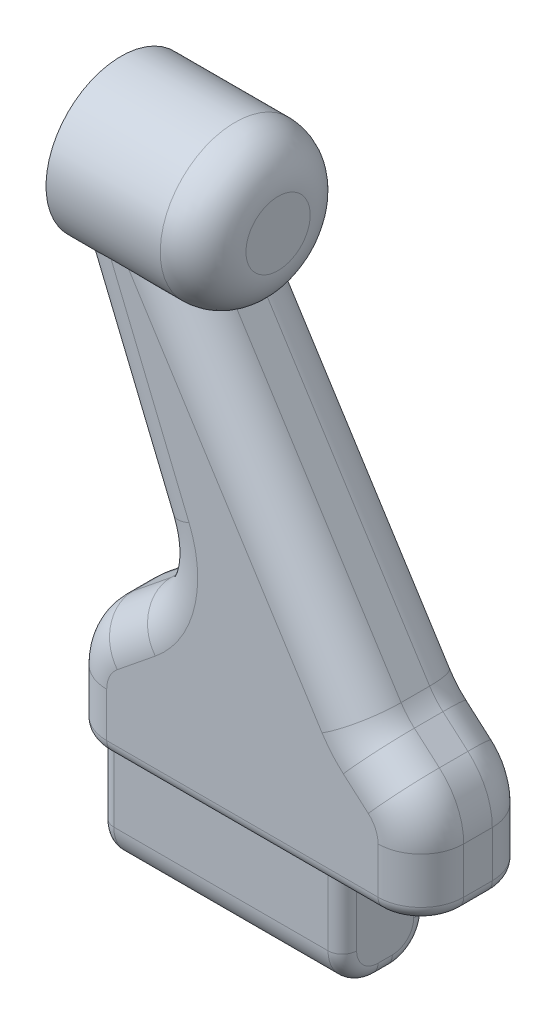
SolidWorks part; units mm, degrees
ref_plane "Front Plane" through (0, 0, 0) normal (0, 0, 1) x (1, 0, 0)
ref_plane "Top Plane" through (0, 0, 0) normal (0, 1, 0) x (1, 0, 0)
ref_plane "Right Plane" through (0, 0, 0) normal (1, 0, 0) x (0, 0, -1)
sketch "Sketch1" plane through (0, 0, 0) normal (0, 0, 1) x (1, 0, 0)
  line L0 (0, 0) -> (5, 0)
  line L2 (1.6, 6.1) -> (0, 6.1)
  line L3 (0, 6.1) -> (1.4829, 2.5)
  line L6 (1.4829, 2.5) -> (0, 1.3)
  line L7 (0, 1.3) -> (0, 0)
  line L8 (0, 1.3) -> (0, 6.1) construction
  line L9 (1.4829, 2.5) -> (3.8829, 2.5) construction
  line L10 (1.6, 6.1) -> (4.2, 2)
  line L11 (4.2, 2) -> (5, 1.3)
  line L12 (5, 1.3) -> (5, 0)
  line L13 (0, 1.3) -> (5, 1.3) construction
  dimension "D1" = 5
  dimension "D2" = 6.1
  dimension "D3" = 1.6
  dimension "D4" = 2.4
  dimension "D5" = 2.5
  dimension "D6" = 1.3
  dimension "D7" = 2
  dimension "D8" = 0.8
extrude "Boss-Extrude1" add sketch "Sketch1" along normal mid plane 1.6
fillet "Fillet1" radius 1 4 edges at (1.4829, 2.5, 0) (0, 1.3, 0) (5, 1.3, 0) (4.2, 2, 0)
fillet "Fillet3" radius 0.6 20 edges at (2.8613, 4.111, -0.8) (4.2079, 2.0067, -0.8) (4.4836, 1.7519, -0.8) (4.9106, 1.2594, -0.8) (2.8613, 4.111, 0.8) (4.2079, 2.0067, 0.8) (4.4836, 1.7519, 0.8) (4.9106, 1.2594, 0.8) (0.5995, 4.6446, 0.8) (1.2433, 2.5611, 0.8) (0.6372, 1.8156, 0.8) (0.0975, 1.2535, 0.8) (0.5995, 4.6446, -0.8) (1.2433, 2.5611, -0.8) (0.6372, 1.8156, -0.8) (0.0975, 1.2535, -0.8) (5, 0.4231, -0.8) (5, 0.4231, 0.8) (0, 0.4114, 0.8) (0, 0.4114, -0.8)
sketch "Sketch3" plane through (0, 0, 0) normal (1, 0, 0) x (0, 0, -1)
  line L0 (0, 0) -> (0, 6.75) construction
  line L1 (0, 6.75) -> (0, 7.8) construction
  circle A0 centre (0, 6.75) radius 1.05
  dimension "D1" = 2.1
  dimension "D2" = 7.8
extrude "Boss-Extrude3" add sketch "Sketch3" along normal blind 2.2
fillet "Fillet4" radius 0.6 1 edges at (2.2, 6.75, -1.05)
sketch "Sketch4" plane through (0, 0, 0) normal (0, 0, 1) x (1, 0, 0)
  line L1 (0.3, 0) -> (3.7, 0)
  line L2 (0.3, 0) -> (0.3, -1.5)
  line L3 (0.3, -1.5) -> (3.7, -1.5)
  line L4 (3.7, 0) -> (3.7, -1.5)
  point P4 (0, 0)
  dimension "D1" = 3.4
  dimension "D2" = 1.5
  dimension "D3" = 0.3
  dimension "D4" = 1.3
extrude "Boss-Extrude4" add sketch "Sketch4" along normal mid plane 1.2
fillet "Fillet5" radius 0.2 8 edges at (0.1757, 0, 0.6243) (0, 0, 0) (0.1757, 0, -0.6243) (2.5, 0, -0.8) (4.8243, 0, -0.6243) (5, 0, 0) (4.8243, 0, 0.6243) (2.5, 0, 0.8)
fillet "Fillet6" radius 0.5 2 edges at (2, -1.5, -0.6) (2, -1.5, 0.6)
fillet "Fillet7" radius 0.2 10 edges at (0.3, -0.4866, -0.6) (0.3, -1.3536, -0.4536) (0.3, -1.5, 0) (0.3, -0.4866, 0.6) (3.7, -0.5, 0.6) (3.7, -0.5, -0.6) (3.7, -1.3536, -0.4536) (3.7, -1.5, 0) (0.3, -1.3536, 0.4536) (3.7, -1.3536, 0.4536)
